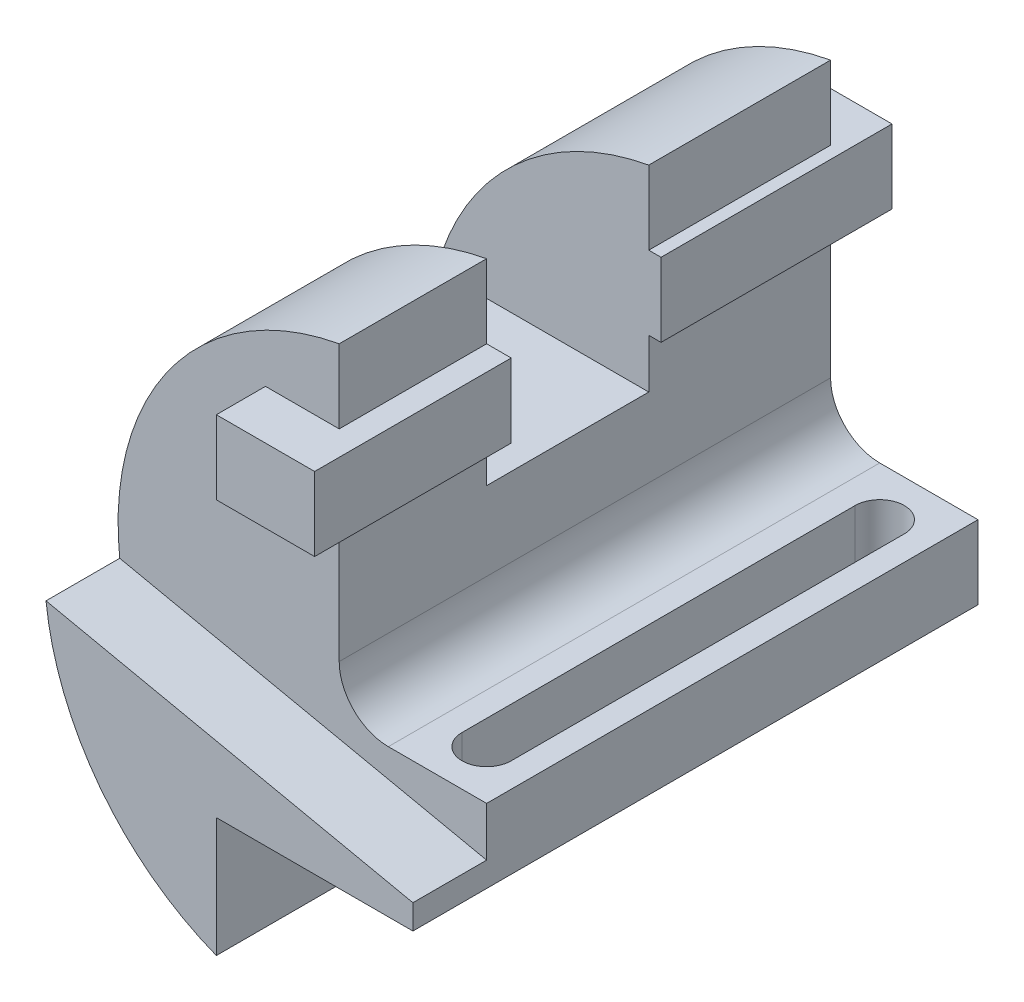
SolidWorks part; units mm, degrees
material "1060 Alloy"
ref_plane "Front Plane" through (0, 0, 0) normal (0, 0, 1) x (1, 0, 0)
ref_plane "Top Plane" through (0, 0, 0) normal (0, 1, 0) x (1, 0, 0)
ref_plane "Right Plane" through (0, 0, 0) normal (1, 0, 0) x (0, 0, -1)
sketch "Sketch1" plane through (0, 0, 0) normal (0, 0, 1) x (1, 0, 0)
  line L0 (0, 55) -> (0, -55) construction
  line L1 (-55, 0) -> (55, 0) construction
  line L2 (-10, 54.0833) -> (-10, -1.9167)
  line L3 (0, -11.9167) -> (20, -11.9167)
  line L4 (20, -11.9167) -> (20, -26.9167)
  line L5 (20, -26.9167) -> (-20, -26.9167)
  line L6 (-20, -26.9167) -> (-20, -51.2348)
  arc A1 (-10, 54.0833) -> (-20, -51.2348) centre (0, 0) ccw
  arc A3 (-10, -1.9167) -> (0, -11.9167) centre (0, -1.9167) ccw
  dimension "D1" = 110
  dimension "D2" = 66
  dimension "D4" = 10
  dimension "D5" = 15
  dimension "D3" = 10
  dimension "D6" = 40
  dimension "D7" = 20
extrude "Boss-Extrude1" add sketch "Sketch1" along normal blind 100
sketch "Sketch4" plane through (-10, 0, 0) normal (1, 0, 0) x (0, 0, -1)
  line L0 (-70, 54.0833) -> (-70, 14.0833)
  line L1 (-100, 54.0833) -> (0, 54.0833) construction
  line L2 (-70, 14.0833) -> (-37, 14.0833)
  line L3 (-37, 14.0833) -> (-37, 54.0833)
  line L4 (-37, 54.0833) -> (-70, 54.0833)
  dimension "D1" = 30
  dimension "D2" = 33
  dimension "D3" = 40
extrude "Cut-Extrude1" cut sketch "Sketch4" against normal up to next
sketch "Sketch5" plane through (-10, 0, 0) normal (1, 0, 0) x (0, 0, -1)
  line L0 (-70, 39.0833) -> (-110, 39.0833)
  line L1 (-70, 54.0833) -> (-70, 14.0833) construction
  line L2 (-110, 39.0833) -> (-110, 24.0833)
  line L3 (-110, 24.0833) -> (-70, 24.0833)
  line L4 (-70, 24.0833) -> (-70, 39.0833)
  dimension "D1" = 15
  dimension "D2" = 15
  dimension "D3" = 40
extrude "Boss-Extrude2" add sketch "Sketch5" along normal mid plane 30
sketch "Sketch6" plane through (5, 0, 0) normal (1, 0, 0) x (0, 0, -1)
  line L0 (-110, 24.0833) -> (-110, 39.0833)
  line L1 (-110, 39.0833) -> (-70, 39.0833)
  line L2 (-70, 39.0833) -> (-70, 24.0833)
  line L3 (-70, 24.0833) -> (-110, 24.0833)
extrude "Cut-Extrude2" cut sketch "Sketch6" against normal blind 10
sketch "Sketch7" plane through (-10, 0, 0) normal (1, 0, 0) x (0, 0, -1)
  line L0 (-37, 39.0833) -> (10, 39.0833)
  line L1 (-37, 14.0833) -> (-37, 54.0833) construction
  line L2 (-37, 24.0833) -> (10, 24.0833)
  line L3 (10, 24.0833) -> (10, 39.0833)
  line L4 (-37, 24.0833) -> (-37, 39.0833)
  line L5 (0, -1.9167) -> (0, 54.0833) construction
  dimension "D1" = 15
  dimension "D2" = 15
  dimension "D3" = 10
extrude "Boss-Extrude3" add sketch "Sketch7" along normal mid plane 5
sketch "Sketch8" plane through (-7.5, 0, 0) normal (1, 0, 0) x (0, 0, -1)
  line L0 (-37, 39.0833) -> (-37, 24.0833)
  line L1 (-37, 24.0833) -> (10, 24.0833)
  line L2 (10, 24.0833) -> (10, 39.0833)
  line L3 (10, 39.0833) -> (-37, 39.0833)
extrude "Boss-Extrude4" add sketch "Sketch8" against normal blind 20
sketch "Sketch9" plane through (0, -11.9167, 0) normal (0, 1, 0) x (1, 0, 0)
  line L0 (10, -10) -> (10, -90) construction
  line L1 (15, -10) -> (15, -90)
  line L2 (5, -10) -> (5, -90)
  line L3 (20, -50) -> (0, -50) construction
  line L4 (20, -100) -> (20, 0) construction
  line L5 (0, -100) -> (0, 0) construction
  arc A0 (15, -10) -> (5, -10) centre (10, -10) ccw
  arc A1 (5, -90) -> (15, -90) centre (10, -90) ccw
  point P2 (10, -50)
  point P13 (0, 0)
  dimension "D2" = 5
  dimension "D1" = 80
extrude "Cut-Extrude3" cut sketch "Sketch9" against normal through all
sketch "Sketch10" plane through (0, 0, 100) normal (0, 0, 1) x (1, 0, 0)
  line L0 (20, -26.9167) -> (20, -21.9167)
  line L1 (20, -26.9167) -> (20, -11.9167) construction
  line L2 (20, -21.9167) -> (-54.6667, -6.0458)
  line L3 (20, -26.9167) -> (-20, -26.9167)
  line L4 (-20, -26.9167) -> (-20, -51.2348)
  arc A0 (-10, 54.0833) -> (-20, -51.2348) centre (0, 0) ccw construction
  arc A1 (-54.6667, -6.0458) -> (-20, -51.2348) centre (0, 0) ccw
  dimension "D1" = 5
  dimension "D3" = 55
  dimension "D2" = 78
extrude "Boss-Extrude5" add sketch "Sketch10" along normal blind 15
equation "\"A\"= 55"
equation "\"B\"= 66"
equation "\"C\"= 33"
